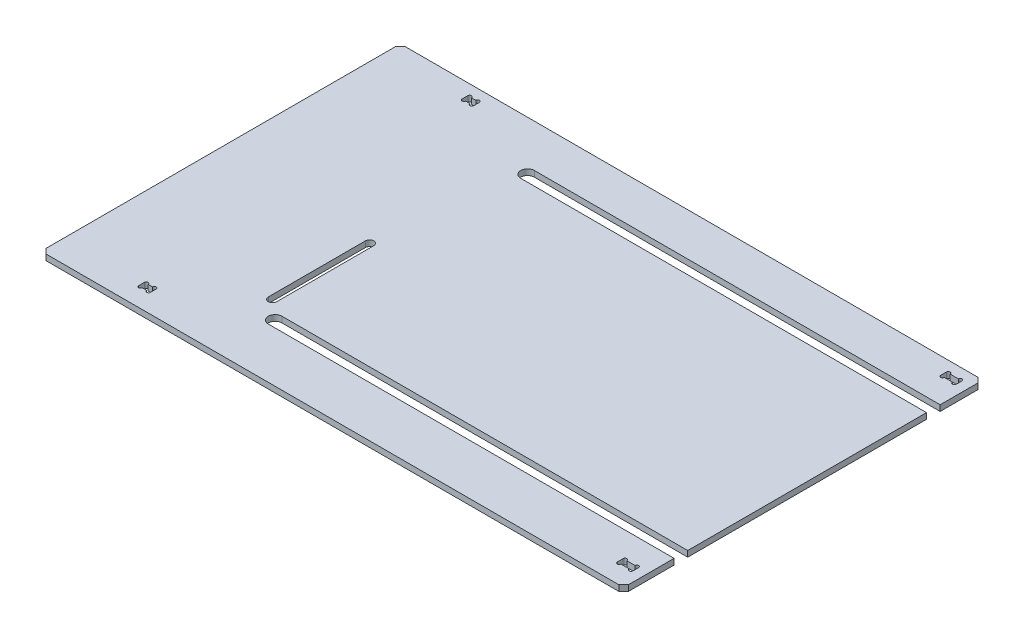
SolidWorks part; units mm, degrees
ref_plane "정면" through (0, 0, 0) normal (0, 0, 1) x (1, 0, 0)
ref_plane "윗면" through (0, 0, 0) normal (0, 1, 0) x (1, 0, 0)
ref_plane "우측면" through (0, 0, 0) normal (1, 0, 0) x (0, 0, -1)
sketch "스케치1" plane through (0, 0, 0) normal (0, 1, 0) x (1, 0, 0)
  line L1 (0, 0) -> (300, 0)
  line L2 (0, 0) -> (0, 185)
  line L3 (0, 185) -> (300, 185)
  line L4 (300, 0) -> (300, 185)
  dimension "D1" = 185
  dimension "D2" = 300
extrude "보스-돌출1" add sketch "스케치1" along normal blind 3
sketch "스케치2" plane through (0, 3, 0) normal (0, 1, 0) x (1, 0, 0)
  line L0 (93, 63.1066) -> (93.0904, 63.1066) construction
  line L1 (93, 60.6066) -> (93, 65.6066) construction
  line L3 (78.9, 63.1066) -> (78.9, 88.1066)
  line L4 (78.9, 38.1066) -> (83.2, 38.1066)
  line L5 (78.9, 38.1066) -> (78.9, 63.1066)
  line L6 (78.9, 88.1066) -> (83.2, 88.1066)
  line L7 (83.2, 38.1066) -> (83.2, 88.1066)
  line L8 (80.1, 83.2292) -> (80.1, 85.4866) construction
  line L10 (81, 83.2292) -> (81, 85.4866) construction
  dimension "D1" = 1.2
  dimension "D2" = 2.2
  dimension "D3" = 25
  dimension "D4" = 25
extrude "컷-돌출1" cut sketch "스케치2" against normal blind 10
sketch "스케치3" plane through (0, 3, 0) normal (0, 1, 0) x (1, 0, 0)
  line L0 (83.2, 88.1066) -> (78.9, 88.1066) construction
  line L1 (78.9, 38.1066) -> (83.2, 38.1066) construction
  circle A0 centre (81.05, 88.1066) radius 2.15
  circle A1 centre (81.05, 38.1066) radius 2.15
extrude "컷-돌출2" cut sketch "스케치3" against normal blind 10
sketch "스케치4" plane through (0, 3, 0) normal (0, 1, 0) x (1, 0, 0)
  line L0 (164.2565, 162) -> (181.1168, 162) construction
  line L1 (300, 163) -> (91, 163)
  line L2 (300, 163) -> (300, 156)
  line L3 (300, 156) -> (91, 156)
  line L4 (91, 163) -> (91, 156)
  line L5 (91, 26) -> (300, 26)
  line L6 (91, 26) -> (91, 33)
  line L7 (91, 33) -> (300, 33)
  line L8 (300, 26) -> (300, 33)
  line L9 (164.2565, 157) -> (181.1168, 157) construction
  line L10 (164.2565, 32) -> (181.1168, 32) construction
  line L13 (300, 0) -> (300, 185) construction
  dimension "D1" = 1
  dimension "D2" = 1
  dimension "D3" = 1
  dimension "D4" = 10
extrude "컷-돌출3" cut sketch "스케치4" against normal blind 10
sketch "스케치5" plane through (0, 3, 0) normal (0, 1, 0) x (1, 0, 0)
  line L0 (91, 163) -> (91, 156) construction
  line L3 (91, 33) -> (91, 26) construction
  circle A0 centre (91, 159.5) radius 3.5
  circle A3 centre (91, 29.5) radius 3.5
extrude "컷-돌출5" cut sketch "스케치5" against normal blind 10
chamfer "모따기1" distance 2.5 angle 45 4 edges at (0, 1.5, 0) (0, 1.5, -185) (300, 1.5, 0) (300, 1.5, -185)
sketch "스케치6" plane through (0, 0, 0) normal (0, -1, 0) x (1, 0, 0)
  line L0 (295, -179.5) -> (295, -9.5) construction
  line L1 (46.5, -179.25) -> (40.5, -179.25)
  line L2 (46.5, -179.25) -> (46.5, -176.25)
  line L3 (46.5, -176.25) -> (40.5, -176.25)
  line L4 (40.5, -179.25) -> (40.5, -176.25)
  line L5 (287, -176.25) -> (295, -176.25)
  line L6 (287, -176.25) -> (287, -179.25)
  line L7 (287, -179.25) -> (295, -179.25)
  line L8 (295, -176.25) -> (295, -179.25)
  line L9 (300, -94.5) -> (244.3606, -94.5) construction
  line L10 (300, -33) -> (300, -156) construction
  line L11 (295, -12.75) -> (295, -9.75)
  line L12 (287, -9.75) -> (295, -9.75)
  line L13 (287, -12.75) -> (287, -9.75)
  line L14 (287, -12.75) -> (295, -12.75)
  line L15 (40.5, -9.75) -> (40.5, -12.75)
  line L16 (46.5, -12.75) -> (40.5, -12.75)
  line L17 (46.5, -9.75) -> (46.5, -12.75)
  line L18 (46.5, -9.75) -> (40.5, -9.75)
  dimension "D1" = 6
  dimension "D2" = 3
  dimension "D3" = 3
extrude "컷-돌출6" cut sketch "스케치6" against normal blind 3
sketch "스케치7" plane through (0, 3, 0) normal (0, 1, 0) x (1, 0, 0)
  line L0 (40.5, 12.75) -> (46.5, 12.75) construction
  line L1 (46.5, 9.75) -> (40.5, 9.75) construction
  line L2 (295, 9.75) -> (287, 9.75) construction
  line L3 (287, 12.75) -> (295, 12.75) construction
  line L4 (23.5484, 94.5) -> (300, 94.5) construction
  line L7 (300, 33) -> (300, 156) construction
  circle A0 centre (41.4422, 12.75) radius 0.9422
  circle A1 centre (45.5578, 12.75) radius 0.9422
  circle A2 centre (45.5578, 9.75) radius 0.9422
  circle A3 centre (41.4422, 9.75) radius 0.9422
  circle A4 centre (294.0578, 9.75) radius 0.9422
  circle A5 centre (294.0578, 12.75) radius 0.9422
  circle A6 centre (287.9422, 12.75) radius 0.9422
  circle A7 centre (287.9422, 9.75) radius 0.9422
  circle A8 centre (287.9422, 179.25) radius 0.9422
  circle A9 centre (287.9422, 176.25) radius 0.9422
  circle A10 centre (294.0578, 176.25) radius 0.9422
  circle A11 centre (294.0578, 179.25) radius 0.9422
  circle A12 centre (41.4422, 179.25) radius 0.9422
  circle A13 centre (45.5578, 179.25) radius 0.9422
  circle A14 centre (45.5578, 176.25) radius 0.9422
  circle A15 centre (41.4422, 176.25) radius 0.9422
  point P36 (300, 94.5)
extrude "컷-돌출7" cut sketch "스케치7" against normal blind 10
